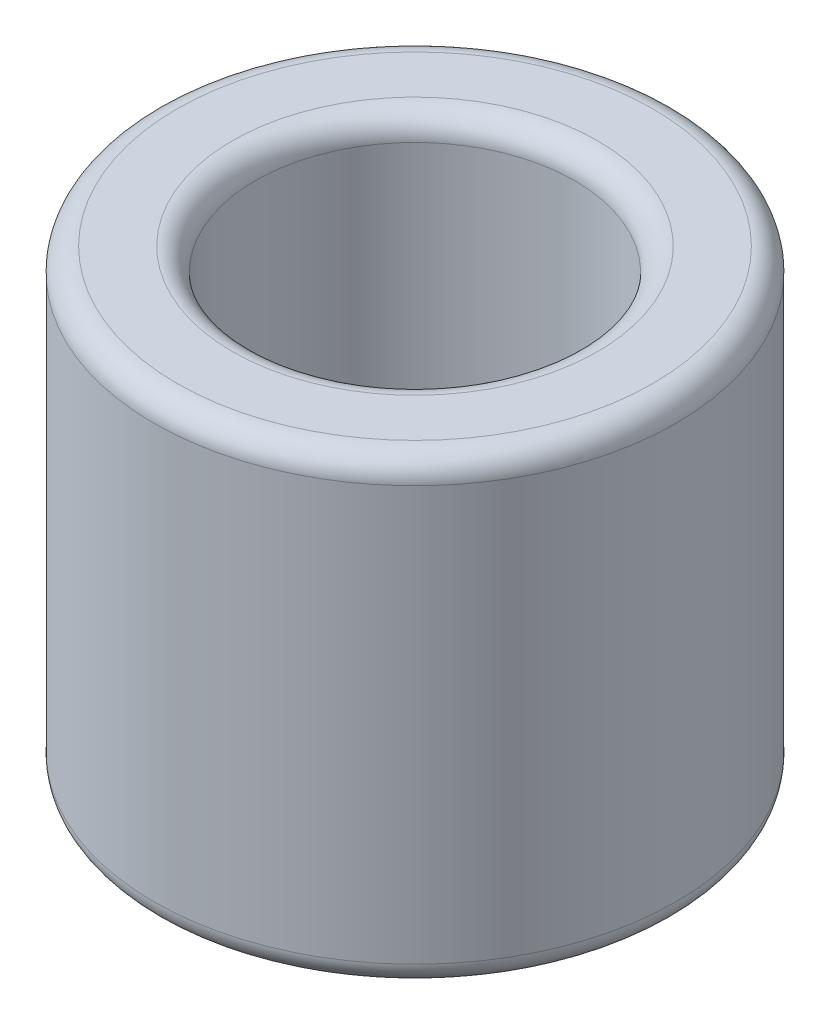
SolidWorks part; units mm, degrees
ref_plane "Front Plane" through (0, 0, 0) normal (0, 0, 1) x (1, 0, 0)
ref_plane "Top Plane" through (0, 0, 0) normal (0, 1, 0) x (1, 0, 0)
ref_plane "Right Plane" through (0, 0, 0) normal (1, 0, 0) x (0, 0, -1)
sketch "Sketch2" plane through (0, 0, 0) normal (0, 1, 0) x (1, 0, 0)
  circle A0 centre (0, 0) radius 3.302
  circle A1 centre (0, 0) radius 5.3975
  dimension "OD" = 10.795
  dimension "ID" = 6.604
extrude "Spacer" add sketch "Sketch2" along normal blind 9.525
fillet "Fillet" radius 0.4762 4 edges at (0, 0, 3.302) (0, 0, 5.3975) (0, 9.525, 3.302) (0, 9.525, 5.3975)
equation "\"OD@Sketch2\"= .425"
equation "\"ID@Sketch2\" = .26in"
equation "\"D1@Spacer\" = .1875 * 2"
equation "\"D1@Fillet\" = \"D1@Spacer\" / 20"
